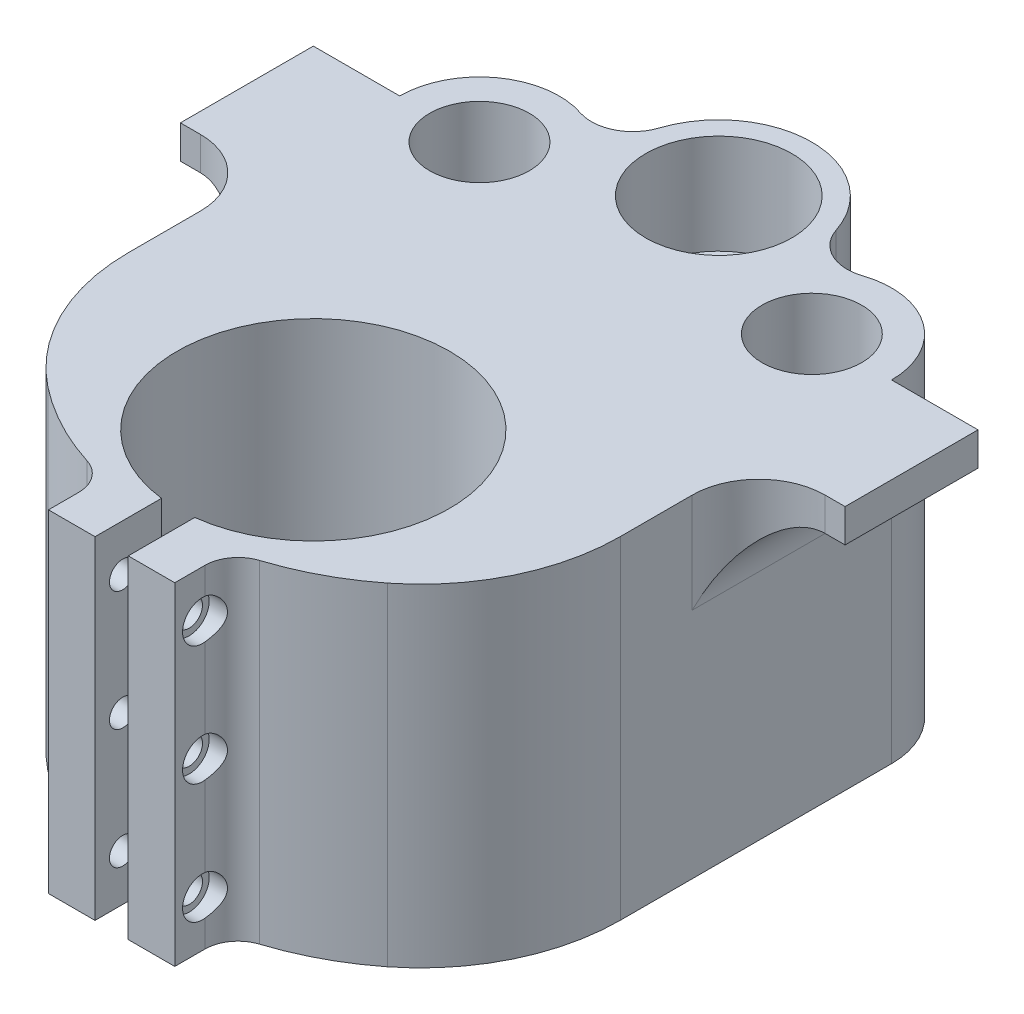
SolidWorks part; units mm, degrees
ref_plane "Front Plane" through (0, 0, 0) normal (0, 0, 1) x (1, 0, 0)
ref_plane "Top Plane" through (0, 0, 0) normal (0, 1, 0) x (1, 0, 0)
ref_plane "Right Plane" through (0, 0, 0) normal (1, 0, 0) x (0, 0, -1)
sketch "Sketch1" plane through (0, 0, 0) normal (0, 1, 0) x (1, 0, 0)
  line L0 (0, -520.2829) -> (0, 25493.863) construction
  line L1 (-520.2829, 0) -> (25493.863, 0) construction
  line L2 (2.5, -70.347) -> (2.5, -80.347)
  line L3 (-2.5, -70.347) -> (-2.5, -80.347)
  line L4 (-1000, -50) -> (49000, -50) construction
  line L9 (37, -1000) -> (37, 49000) construction
  line L10 (-37, -1000) -> (-37, 49000) construction
  line L11 (37, 25) -> (-37, 25)
  line L12 (37, 25) -> (37, -50)
  line L13 (-37, 25) -> (-37, -50)
  line L14 (-1000, -72) -> (49000, -72) construction
  line L15 (2.5, -80.347) -> (9.5, -80.347)
  line L16 (9.5, -80.347) -> (9.5, -72)
  line L17 (-2.5, -80.347) -> (-9.5, -80.347)
  line L18 (-9.5, -80.347) -> (-9.5, -72)
  circle A0 centre (25, 0) radius 7.5
  circle A1 centre (-25, 0) radius 7.5
  circle A2 centre (0, 11) radius 5.1
  arc A3 (2.5, -70.347) -> (-2.5, -70.347) centre (0, -50) ccw
  arc A6 (37, -50) -> (9.5, -72) centre (0.8136, -32.9546) cw
  arc A7 (-37, -50) -> (-9.5, -72) centre (-0.8136, -32.9546) ccw
  dimension "D1" = 15
  dimension "D2" = 25
  dimension "D3" = 11
  dimension "D4" = 10.2
  dimension "D5" = 37
  dimension "D8" = 20.5
  dimension "D10" = 72
  dimension "D13" = 40
  dimension "D6" = 50
  dimension "D7" = 2.5
  dimension "D9" = 25
  dimension "D11" = 10
  dimension "D12" = 7
extrude "Boss-Extrude1" add sketch "Sketch1" along normal blind 50
sketch "Sketch4" plane through (0, 50, 0) normal (0, 1, 0) x (1, 0, 0)
  line L0 (0, -1000) -> (0, 49000) construction
  line L1 (-1000, 0) -> (49000, 0) construction
  circle A0 centre (0, 11) radius 11
  dimension "D1" = 22
extrude "Cut-Extrude1" cut sketch "Sketch4" against normal blind 15
sketch "Sketch5" plane through (0, 35, 0) normal (0, 1, 0) x (1, 0, 0)
  line L0 (-1000, 0) -> (49000, 0) construction
  line L1 (0, -1000) -> (0, 49000) construction
  circle A0 centre (0, 11) radius 8 construction
  circle A1 centre (0, 19) radius 1.5
  circle A2 centre (8, 11) radius 1.5
  circle A3 centre (0, 3) radius 1.5
  circle A4 centre (-8, 11) radius 1.5
  point P19 (0, 11)
  dimension "D1" = 16
  dimension "D2" = 3
  dimension "D4" = 8
  dimension "D5" = 11
  dimension "D3" = 4
extrude "Cut-Extrude2" cut sketch "Sketch5" against normal up to next
sketch "Sketch7" plane through (0, 0, -25) normal (0, 0, -1) x (-1, 0, 0)
  line L5 (0, -1000) -> (0, 49000) construction
  line L6 (-37, 0) -> (37, 0) construction
  line L7 (-12.5, 0) -> (12.5, 0)
  line L8 (-12.5, 0) -> (-12.5, 10)
  line L9 (-12.5, 10) -> (12.5, 10)
  line L10 (12.5, 0) -> (12.5, 10)
  point P7 (0, 10)
  dimension "D1" = 25
  dimension "D2" = 10
extrude "Cut-Extrude3" cut sketch "Sketch7" against normal blind 25
fillet "Fillet1" radius 25 3 edges at (24.75, 0, -25) (37, 25, -25) (12.5, 5, -25)
fillet "Fillet2" radius 25 3 edges at (-37, 25, -25) (-24.75, 0, -25) (-12.5, 5, -25)
sketch "Sketch9" plane through (-9.5, 0, 0) normal (-1, 0, 0) x (0, 0, 1)
  line L0 (76.1735, -950) -> (76.1735, 49050) construction
  line L1 (80.347, 50) -> (72, 50) construction
  line L2 (-940.6351, 25) -> (49059.3649, 25) construction
  line L3 (80.347, 50) -> (80.347, 0) construction
  circle A0 centre (76.1735, 43) radius 2
  circle A1 centre (76.1735, 7) radius 2
  circle A2 centre (76.1735, 25) radius 2
  point P5 (76.1735, 50)
  point P10 (80.347, 25)
  dimension "D1" = 4
  dimension "D2" = 18
extrude "Cut-Extrude4" cut sketch "Sketch9" against normal up to surface (19 mm away) up to face at (9.5, 25, 76.1735)
fillet "Fillet3" radius 5 1 edges at (-9.5, 25, 72) type face fillet first side face at (-24.5257, 25, 62.5947) second side face at (-9.5, 43, 78.1735)
fillet "Fillet4" radius 5 1 edges at (9.5, 25, 72) type face fillet first side face at (24.5257, 25, 62.5947) second side face at (9.5, 43, 78.1735)
sketch "Sketch10" plane through (-9.5, 0, 0) normal (-1, 0, 0) x (0, 0, 1)
  line L0 (-939.653, 25) -> (49060.347, 25) construction
  line L1 (80.347, 50) -> (80.347, 0) construction
  circle A0 centre (76.1735, 7) radius 3
  circle A1 centre (76.1735, 43) radius 3
  circle A2 centre (76.1735, 25) radius 3
  point P5 (80.347, 25)
  dimension "D1" = 6
extrude "Cut-Extrude5" cut sketch "Sketch10" against normal blind 2 and the other way blind 2
ref_plane "Plane1" through (0, 0, 0) normal (1, 0, 0) x (0, 0, -1)
mirror "Mirror1" about plane through (0, 0, 0) normal (1, 0, 0) of "Cut-Extrude5"
sketch "Sketch11" plane through (0, 50, 0) normal (0, 1, 0) x (1, 0, 0)
  line L0 (0, -1000) -> (0, 49000) construction
  line L1 (12, 25) -> (-12, 25) construction
  line L2 (12, 25) -> (-12, 25)
  circle A0 centre (-25, 0) radius 12
  circle A1 centre (0, 11) radius 14
  arc A4 (-12, 25) -> (-37, 0) centre (-12, 0) ccw construction
  arc A5 (-12, 25) -> (-37, 0) centre (-12, 0) ccw
  arc A6 (37, 0) -> (12, 25) centre (12, 0) ccw construction
  arc A7 (37, 0) -> (12, 25) centre (12, 0) ccw
  arc A8 (-21.2072, 11.3849) -> (-13.3031, 15.362) centre (-19.2344, 17.3069) ccw
  circle A9 centre (25, 0) radius 12
  arc A10 (21.2072, 11.3849) -> (13.3031, 15.362) centre (19.2344, 17.3069) cw
  dimension "D2" = 28
extrude "Cut-Extrude6" cut sketch "Sketch11" against normal through all
fillet "Fillet5" radius 30 1 edges at (-37, 25, 50) type face fillet first side face at (-37, 25, 25) second side face at (-26.0864, 25, 61.7808)
fillet "Fillet6" radius 30 1 edges at (37, 25, 50) type face fillet first side face at (37, 25, 25) second side face at (26.0864, 25, 61.7808)
sketch "Sketch13" plane through (0, 50, 0) normal (0, 1, 0) x (1, 0, 0)
  line L0 (0, -1000) -> (0, 49000) construction
  line L1 (37, 0) -> (37, -40.8113) construction
  line L2 (37, 0) -> (50, 0)
  line L3 (37, 0) -> (37, -20)
  line L4 (37, -20) -> (50, -20)
  line L5 (50, 0) -> (50, -20)
  line L6 (-1000, 0) -> (49000, 0) construction
  dimension "D1" = 13
  dimension "D2" = 20
extrude "Boss-Extrude2" add sketch "Sketch13" against normal blind 5
mirror "Mirror2" about plane through (0, 0, 0) normal (1, 0, 0) of "Boss-Extrude2"
fillet "Fillet7" radius 10 2 edges at (37, 47.5, 20) (37, 45, 10) type face fillet first side face at (43.5, 47.5, 20) first side face at (43.5, 45, 10) second side face at (37, 31.6667, 20.2704)
fillet "Fillet13" radius 10 2 edges at (-37, 47.5, 20) (-37, 45, 10) type face fillet first side face at (-43.5, 47.5, 20) first side face at (-43.5, 45, 10) second side face at (-37, 31.6667, 20.2704)
